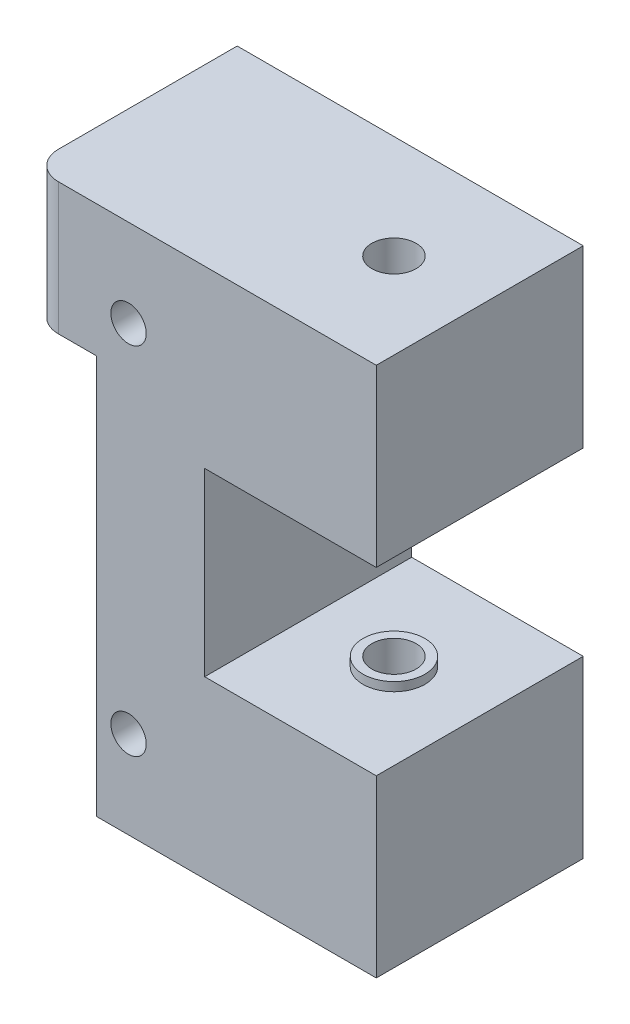
SolidWorks part; units mm, degrees
ref_plane "Front Plane" through (0, 0, 0) normal (0, 0, 1) x (1, 0, 0)
ref_plane "Top Plane" through (0, 0, 0) normal (0, 1, 0) x (1, 0, 0)
ref_plane "Right Plane" through (0, 0, 0) normal (1, 0, 0) x (0, 0, -1)
sketch "MainBlock" plane through (0, 0, 0) normal (0, 0, 1) x (1, 0, 0)
  line L0 (0, 0) -> (39.125, 0)
  line L1 (39.125, 0) -> (39.125, 19.8)
  line L2 (39.125, 19.8) -> (19.725, 19.8)
  line L3 (19.725, 19.8) -> (19.725, 40.2)
  line L4 (19.725, 40.2) -> (39.125, 40.2)
  line L5 (39.125, 40.2) -> (39.125, 60)
  line L6 (39.125, 60) -> (0, 60)
  line L7 (0, 60) -> (0, 0)
  circle A0 centre (11.1125, 50.1) radius 2
  circle A1 centre (11.1125, 9.9) radius 2
  dimension "D4" = 4
  dimension "D1" = 39.125
  dimension "D2" = 60
  dimension "D3" = 20.4
  dimension "D5" = 19.4
  dimension "D6" = 11.1125
  dimension "D7" = 9.9
  dimension "D8" = 9.9
  dimension "D9" = 19.8
  dimension "D10" = 19.8
extrude "MainBlockBoss-Extrude1" add sketch "MainBlock" along normal blind 23.4
sketch "TopHoleCut-Sketch2" plane through (0, 60, 0) normal (0, 1, 0) x (1, 0, 0)
  line L0 (39.125, 0) -> (0, 0) construction
  circle A0 centre (29.425, -11.7) radius 2.5
  dimension "D3" = 5
  dimension "D1" = 11.7
  dimension "D2" = 9.7
extrude "TopHoleCut-Extrude1" cut sketch "TopHoleCut-Sketch2" against normal blind 45
sketch "TopSpacerSketch4" plane through (0, 40.2, 0) normal (0, -1, 0) x (1, 0, 0)
  circle A0 centre (29.425, 11.7) radius 3.5
  circle A1 centre (29.425, 11.7) radius 2.5
  circle A2 centre (29.425, 11.7) radius 2.5 construction
  dimension "D1" = 7
extrude "TopSpacerBoss-Extrude2" add sketch "TopSpacerSketch4" along normal blind 1
sketch "LowerSpacerSketch5" plane through (0, 19.8, 0) normal (0, 1, 0) x (1, 0, 0)
  circle A0 centre (29.425, -11.7) radius 2.5
  circle A1 centre (29.425, -11.7) radius 2.5 construction
  circle A2 centre (29.425, -11.7) radius 3.5
  circle A3 centre (29.425, -11.7) radius 3.5 construction
extrude "LowerSpacerBoss-Extrude3" add sketch "LowerSpacerSketch5" along normal blind 1
sketch "MountHoleBoreSketch1" plane through (0, 0, 0) normal (0, 0, -1) x (-1, 0, 0)
  line L1 (-7.2375, 50.1) -> (-9.175, 53.4558)
  line L2 (-9.175, 53.4558) -> (-13.05, 53.4558)
  line L3 (-13.05, 53.4558) -> (-14.9875, 50.1)
  line L4 (-14.9875, 50.1) -> (-13.05, 46.7442)
  line L5 (-13.05, 46.7442) -> (-9.175, 46.7442)
  line L6 (-9.175, 46.7442) -> (-7.2375, 50.1)
  line L7 (-7.2375, 9.9) -> (-9.175, 13.2558)
  line L8 (-9.175, 13.2558) -> (-13.05, 13.2558)
  line L9 (-13.05, 13.2558) -> (-14.9875, 9.9)
  line L10 (-14.9875, 9.9) -> (-13.05, 6.5442)
  line L11 (-13.05, 6.5442) -> (-9.175, 6.5442)
  line L12 (-9.175, 6.5442) -> (-7.2375, 9.9)
  circle A0 centre (-11.1125, 50.1) radius 3.3558 construction
  circle A1 centre (-11.1125, 9.9) radius 3.3558 construction
  dimension "D1" = 7.75
extrude "MountHoleBoreCut-Extrude1" cut sketch "MountHoleBoreSketch1" against normal blind 2
sketch "PushPinHoleSketch1" plane through (0, 0, 0) normal (0, -1, 0) x (1, 0, 0)
  circle A0 centre (29.425, 11.7) radius 1
  circle A1 centre (29.425, 11.7) radius 2.5 construction
  dimension "D1" = 2
extrude "PushPinHoleCut-Extrude1" cut sketch "PushPinHoleSketch1" against normal through all
sketch "MidRailInsetSketch1" plane through (0, 0, 0) normal (0, 0, -1) x (-1, 0, 0)
  line L0 (0, 60) -> (0, 0) construction
  line L1 (0, 45.1) -> (-7.5, 45.1)
  line L2 (0, 45.1) -> (0, 0)
  line L3 (0, 0) -> (-7.5, 0)
  line L4 (-7.5, 45.1) -> (-7.5, 0)
  line L6 (0, 0) -> (-39.125, 0) construction
  line L7 (-39.125, 60) -> (0, 60) construction
  dimension "D1" = 7.5
  dimension "D2" = 14.9
extrude "MidRailInsetCut-Extrude2" cut sketch "MidRailInsetSketch1" against normal through all
fillet "VerticalSupportFillet1" radius 3.175 1 edges at (0, 52.55, 23.4)
equation "\"BeltTensionerWidth\"= \"MidRailToAlignWithGantryBlock\" + \"BeltTensionerInnerWidth\" / 2 + \"RailThickness\""
equation "\"BeltTensionerHeight\"= 60mm"
equation "\"BeltTensionerDepth\"= \"BeltTensionerBackWallThickness\" + \"BeltTensionerInnerDepth\"'Equals 23.4"
equation "\"BeltTensionerInnerWidth\"= \"20TGT2PulleyDiameter\" + \"BeltTensionerSpaceBetweenPulleyAndWall\""
equation "\"BeltTensionerInnerHeight\"= \"20TGT2PulleyWidth\" * 2 + \"1mmSpacer\" * 3"
equation "\"BeltTensionerBackWallThickness\"= 4mm"
equation "\"BeltTensionerInnerDepth\"= \"20TGT2PulleyDiameter\" + \"BeltTensionerSpaceBetweenPulleyAndWall\""
equation "\"RailThickness\"= .125in'Spec"
equation "\"HoleOffsetFromEdge\"= \"RailThickness\" * 2.5"
equation "\"LinearGBWithRailDepth\"= 12.75mm'Spec"
equation "\"GABDistanceFromBackToFirstPulley\"= 13.5mm"
equation "\"MidRailToAlignWithGantryBlock\"= \"LinearGBWithRailDepth\" + \"GABDistanceFromBackToFirstPulley\"'All outside cogs must align"
equation "\"20TGT2PulleyDiameter\"= 17.9mm'Spec"
equation "\"BeltTensionerSpaceBetweenPulleyAndWall\"= 1.5mm"
equation "\"BeltTensionerMountingHoleDiameter\"= 4.0mm"
equation "\"BeltTensionerMountingHoleOffsetFromEdge\"= \"HoleOffsetFromEdge\""
equation "\"20TGT2PulleyWidth\"= 8.7mm'The STL of the Pulley in the diagram is a bit larger"
equation "\"1mmSpacer\"= 1mm"
equation "\"SteelShaft5mmHoleDiameter\"= 5mm"
equation "\"BeltTensionerMountingHoleOuterBoreDepth\"= 2mm"
equation "\"BeltTensionerMountingHoleOuterBoreDiameter\"= 7.75mm"
equation "\"7mmx1mmSpacerDiameter\"= 7mm"
equation "\"7mmx1mmSpacerHeight\"= 1mm"
equation "\"D1@MainBlock\" = \"BeltTensionerWidth\""
equation "\"D4@MainBlock\" = \"BeltTensionerMountingHoleDiameter\""
equation "\"D5@MainBlock\" = \"BeltTensionerInnerWidth\""
equation "\"D6@MainBlock\"=\"BeltTensionerMountingHoleOffsetFromEdge\" + \"RailThickness\""
equation "\"D7@MainBlock\"=\"BeltTensionerMountingHoleOffstFromTopOrBottom\""
equation "\"D8@MainBlock\"=\"BeltTensionerMountingHoleOffstFromTopOrBottom\""
equation "\"D1@MainBlockBoss-Extrude1\" = \"BeltTensionerDepth\""
equation "\"D1@TopHoleCut-Sketch2\" = \"BeltTensionerDepth\" / 2"
equation "\"D3@TopHoleCut-Sketch2\" = \"SteelShaft5mmHoleDiameter\""
equation "\"D1@TopSpacerSketch4\" = \"7mmx1mmSpacerDiameter\""
equation "\"D1@TopSpacerBoss-Extrude2\" = \"7mmx1mmSpacerHeight\""
equation "\"D1@LowerSpacerBoss-Extrude3\" = \"7mmx1mmSpacerHeight\""
equation "\"D1@MountHoleBoreSketch1\" = \"BeltTensionerMountingHoleOuterBoreDiameter\""
equation "\"D1@MountHoleBoreCut-Extrude1\" = \"BeltTensionerMountingHoleOuterBoreDepth\""
equation "\"SteelPinPushHoleDiameter\"= 2mm"
equation "\"D1@PushPinHoleSketch1\" = \"SteelPinPushHoleDiameter\""
equation "\"D2@TopHoleCut-Sketch2\"=\"BeltTensionerWidth\" - \"MidRailToAlignWithGantryBlock\" - \"RailThickness\""
equation "\"BeltTensionerMountingHoleOffstFromTopOrBottom\"= ( \"BeltTensionerHeight\" - \"BeltTensionerInnerHeight\" ) / 4"
equation "\"BeltTensionerSteelShaftHoleDepthFromTop\"= ( \"SteelShaftLength\" - \"BeltTensionerInnerHeight\" ) / 2 + ( \"BeltTensionerHeight\" - \"BeltTensionerInnerHeight\" ) / 2 + \"BeltTensionerInnerHeight\"'Equals 45"
equation "\"SteelShaftLength\"= 30mm"
equation "\"D1@TopHoleCut-Extrude1\"=\"BeltTensionerSteelShaftHoleDepthFromTop\""
equation "\"MidSideRailVerticalOffset\"= \"LinearRailWidth\" + 3mm'Allows space for RodStabilizer to attach to bottom of MidSideRail"
equation "\"LinearRailWidth\"= 12mm'Spec"
equation "\"D2@MidRailInsetSketch1\"=\"DistanceAboveMidSideRailToTopOfBeltTensioner\""
equation "\"DistanceAboveMidSideRailToTopOfBeltTensioner\"= \"VS ToTopOfBeltTensionerAlignedWithYAxisGantryBlockUpperPulley\" - \"V8 ToTopOfMidSideRail\"'Equals 14.9"
equation "\"DistanceFromBeltTensionerTopPulleyToBeltTensionerTop\"= \"7mmx1mmSpacerHeight\" + \"BeltTensionerTopHeight\"'Equals 20.8"
equation "\"BeltTensionerTopHeight\"= ( \"BeltTensionerHeight\" - \"BeltTensionerInnerHeight\" ) / 2'Equals 19.8"
equation "\"GABUpperHeight\"= 4mm"
equation "\"D3@MainBlock\"=\"BeltTensionerInnerHeight\""
equation "\"D9@MainBlock\"=\"BeltTensionerTopHeight\""
equation "\"LegHeight\"= 70mm'Space needed for PSU/Stepper/Electronics"
equation "\"V1 BottomOfLowerRail\"= \"LegHeight\""
equation "\"LowerEnclosureThickness\"= 5mm"
equation "\"StepperShaftLength\"= 24mm'Pulley will be attached to the end"
equation "\"ZAxisLeadScrewLength\"= 200mm"
equation "\"LM8UUHeight\"= 24mm'Spec"
equation "\"V2 ToBedAtTopOfZAxis\"= \"V1 BottomOfLowerRail\" - \"LowerEnclosureThickness\" + \"StepperShaftLength\" + \"ZAxisLeadScrewLength\" - \"LM8UUHeight\" / 2'Equals 277"
equation "\"BedToBuildPlateStandoffLength\"= 15mm"
equation "\"BuildPlateHeight\"= 8mm'Spec"
equation "\"V4 ToTopOfBuildPlate/HotEndTip\"= \"V2 ToBedAtTopOfZAxis\" + \"BedToBuildPlateStandoffLength\" + \"BuildPlateHeight\""
equation "\"HotEndToTopOfXAxisGB\"= 71.68487mm'Equals 71.68487. Measured after installed onto X-Axis linear rail guide block"
equation "\"LinearGBWidth\"= 27mm'Spec"
equation "\"TopOfGBToBottomOfLinearRail\"= \"LinearGBWidth\" / 2 + \"LinearRailWidth\" / 2'Equals 19.5"
equation "\"V5 ToBottomOfXAxisLinearRail\"= \"V4 ToTopOfBuildPlate/HotEndTip\" + \"HotEndToTopOfXAxisGB\" - \"TopOfGBToBottomOfLinearRail\"'Equals 352.18487"
equation "\"GABMidWallHeight\"= 28mm'Must equal 28 or changes alignment"
equation "\"GABLowerHeight\"= 4mm"
equation "\"GABHeight\"= \"GABLowerHeight\" + \"GABMidWallHeight\" + \"GABUpperHeight\""
equation "\"V6 ToMiddleOfYAxisGantryBlock\"= \"V5 ToBottomOfXAxisLinearRail\" - \"GABHeight\" / 2'Equals 334.18487"
equation "\"V8 ToTopOfMidSideRail\"= \"V6 ToMiddleOfYAxisGantryBlock\" + \"MidSideRailVerticalOffset\"'Equals 349.18487"
equation "\"VS ToTopOfBeltTensionerAlignedWithYAxisGantryBlockUpperPulley\"= \"V5 ToBottomOfXAxisLinearRail\" - \"DistanceFromXAxisLinearRailBottomAndTopOfGantryPulley\" + \"DistanceFromBeltTensionerTopPulleyToBeltTensionerTop\"'Equals 364.08487"
equation "\"GABRiserBossOffset\"= 0.4mm'Aligns Pulleys inside edges to be 2.5mm (.5mm apart top to bottom)"
equation "\"GABMidShortRiserHeight\"= \"GABMidWallHeight\" / 2 - \"20TGT2PulleyWidth\"'Equals 5.3"
equation "\"DistanceFromXAxisLinearRailBottomAndTopOfGantryPulley\"= \"GABUpperHeight\" + \"GABMidShortRiserHeight\" - \"GABRiserBossOffset\"'Equals 8.9"
equation "\"D1@VerticalSupportFillet1\"=\"RailThickness\""
